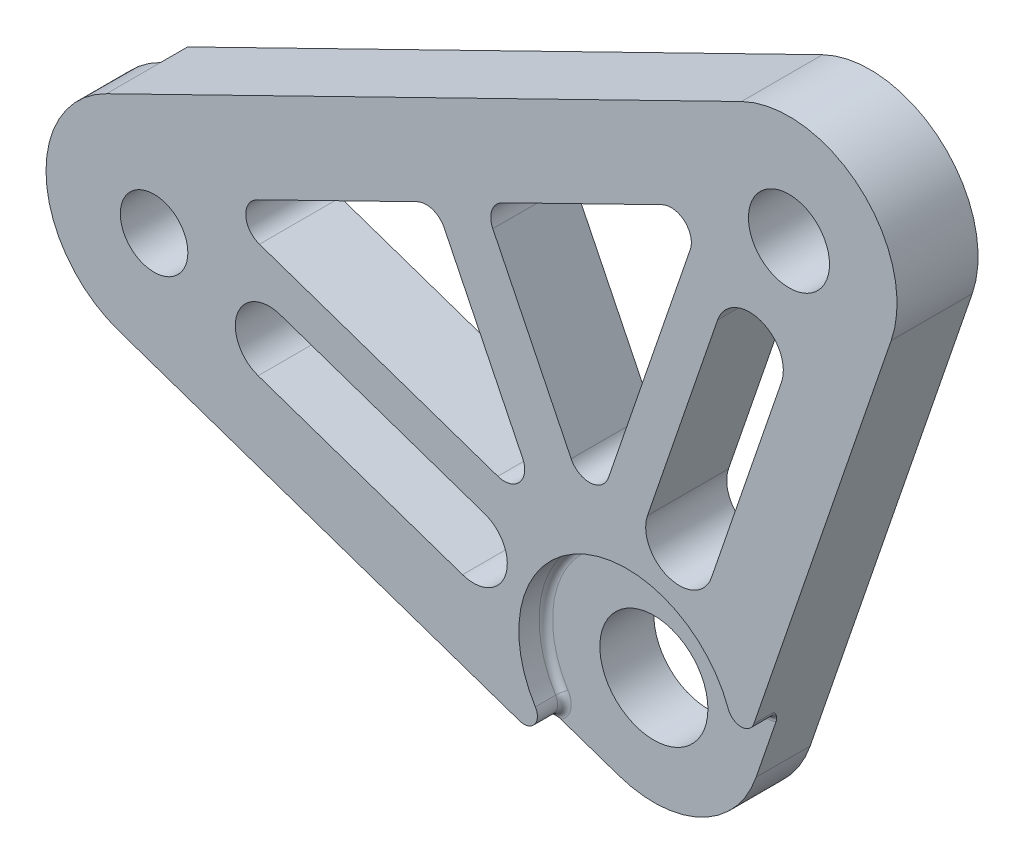
SolidWorks part; units mm, degrees
material "AISI 1045 Steel, cold drawn"
ref_plane "Front Plane" through (0, 0, 0) normal (0, 0, 1) x (1, 0, 0)
ref_plane "Top Plane" through (0, 0, 0) normal (0, 1, 0) x (1, 0, 0)
ref_plane "Right Plane" through (0, 0, 0) normal (1, 0, 0) x (0, 0, -1)
sketch "Sketch1" plane through (0, 0, 0) normal (0, 0, 1) x (1, 0, 0)
  line L2 (0, 0) -> (-35, 12) construction
  line L3 (0, 32.1948) -> (0, -15.8001) construction
  line L4 (19.5676, 32.4054) -> (7.5676, -2.5946)
  line L5 (0, 0) -> (12, 35) construction
  line L6 (-37.5946, 4.4324) -> (-2.5946, -7.5676)
  line L7 (8.4836, 42.1857) -> (-38.5164, 19.1857)
  circle A1 centre (-35, 12) radius 2.5
  arc A2 (-38.5164, 19.1857) -> (-37.5946, 4.4324) centre (-35, 12) ccw
  circle A3 centre (0, 0) radius 4
  circle A6 centre (12, 35) radius 3
  arc A9 (19.5676, 32.4054) -> (8.4836, 42.1857) centre (12, 35) ccw
  arc A10 (-2.5946, -7.5676) -> (7.5676, -2.5946) centre (0, 0) ccw
  dimension "D4" = 5
  dimension "D6" = 8
  dimension "D10" = 6
  dimension "D5" = 8
  dimension "D7" = 8
  dimension "D8" = 8
  dimension "D3" = 35
  dimension "D9" = 12
  dimension "D2" = 35
  dimension "D11" = 12
extrude "Boss-Extrude1" add sketch "Sketch1" along normal blind 6 contours A1 | A3 | A6 | L7 A2 L6 A10 L4 A9 region at (-35, 12, 0) region at (0, 0, 0) region at (12, 35, 0)
sketch "Sketch2" plane through (0, 0, 6) normal (0, 0, 1) x (1, 0, 0)
  line L0 (-27.3725, 17.9592) -> (-15.5229, 23.758)
  line L1 (-13.5162, 23.07) -> (-7.7175, 11.2204)
  line L2 (-9.5513, 9.1421) -> (-27.1996, 15.193)
  line L3 (-1.3187, 2.6947) -> (-18.3673, 37.5333) construction
  line L4 (-26.4865, 9.0811) -> (-11.3514, 3.8919) construction
  line L5 (8.4836, 42.1857) -> (-38.5164, 19.1857) construction
  line L6 (-25.6757, 11.4459) -> (-10.5405, 6.2568)
  line L7 (-33.1957, 11.3814) -> (1.8043, -0.6186) construction
  line L8 (-37.5946, 4.4324) -> (-2.5946, -7.5676) construction
  line L12 (-27.2973, 6.7162) -> (-12.1622, 1.527)
  line L14 (-10.4555, 6.5048) -> (-3.0085, 28.2253) construction
  line L15 (-9.9233, 24.8282) -> (-4.1246, 12.9786)
  line L16 (2.6143, 32.6336) -> (-9.2353, 26.8349)
  line L17 (-1.3583, 13.1514) -> (4.6925, 30.7998)
  line L18 (9.0811, 26.4865) -> (3.8919, 11.3514) construction
  line L19 (6.7162, 27.2973) -> (1.527, 12.1622)
  line L20 (11.4459, 25.6757) -> (6.2568, 10.5405)
  arc A0 (-7.7175, 11.2204) -> (-9.5513, 9.1421) centre (-9.0648, 10.561) cw
  arc A1 (-27.3725, 17.9592) -> (-27.1996, 15.193) centre (-26.7132, 16.6119) ccw
  arc A2 (-15.5229, 23.758) -> (-13.5162, 23.07) centre (-14.8635, 22.4107) cw
  arc A6 (-25.6757, 11.4459) -> (-27.2973, 6.7162) centre (-26.4865, 9.0811) ccw
  arc A7 (-12.1622, 1.527) -> (-10.5405, 6.2568) centre (-11.3514, 3.8919) ccw
  arc A8 (-9.2353, 26.8349) -> (-9.9233, 24.8282) centre (-8.576, 25.4875) ccw
  arc A9 (-4.1246, 12.9786) -> (-1.3583, 13.1514) centre (-2.7773, 13.6379) ccw
  arc A10 (2.6143, 32.6336) -> (4.6925, 30.7998) centre (3.2736, 31.2863) cw
  arc A11 (6.7162, 27.2973) -> (11.4459, 25.6757) centre (9.0811, 26.4865) cw
  arc A12 (6.2568, 10.5405) -> (1.527, 12.1622) centre (3.8919, 11.3514) cw
  point P8 (-15.0164, 30.6857)
  point P17 (-18.9189, 6.4865)
  point P41 (6.4865, 18.9189)
  dimension "D4" = 1.5
  dimension "D3" = 2.5
  dimension "D1" = 2
  dimension "D2" = 12
  dimension "D5" = 16
  dimension "D6" = 6
extrude "Cut-Extrude1" cut sketch "Sketch2" against normal through all both and the other way through all
sketch "Sketch4" plane through (0, 0, 6) normal (0, 0, 1) x (1, 0, 0)
  circle A0 centre (0, 0) radius 8
  circle A1 centre (-35, 12) radius 8
  circle A2 centre (-35, 12) radius 2.5 construction
  arc A3 (-38.5164, 19.1857) -> (-37.5946, 4.4324) centre (-35, 12) ccw construction
  dimension "D1" = 16
extrude "Cut-Extrude2" cut sketch "Sketch4" against normal blind 2 contours A0
fillet "Fillet1" radius 1 2 edges at (7.5676, -2.5946, 5) (-2.5946, -7.5676, 5)
fillet "Fillet2" radius 0.5 3 edges at (-6.8376, -5.4081, 4) (-3.5164, 7.1857, 4) (8.4658, 2.0809, 4)
sketch "Sketch5" plane through (0, 0, 0) normal (0, 0, -1) x (-1, 0, 0)
  line L1 (-8.4836, 42.1857) -> (38.5164, 19.1857) construction
  line L2 (37.5946, 4.4324) -> (32.3214, 7.778)
  line L3 (32.8678, 16.5226) -> (38.5164, 19.1857)
  circle A1 centre (35, 12) radius 5 construction
  arc A2 (38.5164, 19.1857) -> (37.5946, 4.4324) centre (35, 12) cw
  arc A3 (32.3214, 7.778) -> (32.8678, 16.5226) centre (35, 12) cw
  arc A4 (37.5946, 4.4324) -> (38.5164, 19.1857) centre (35, 12) ccw construction
  dimension "D1" = 10
extrude "Cut-Extrude3" cut sketch "Sketch5" against normal blind 2
ref_point "Point1"
ref_point "Point2"
ref_point "Point3"
equation "\"D7@Sketch1\"=\"D5@Sketch1\""
